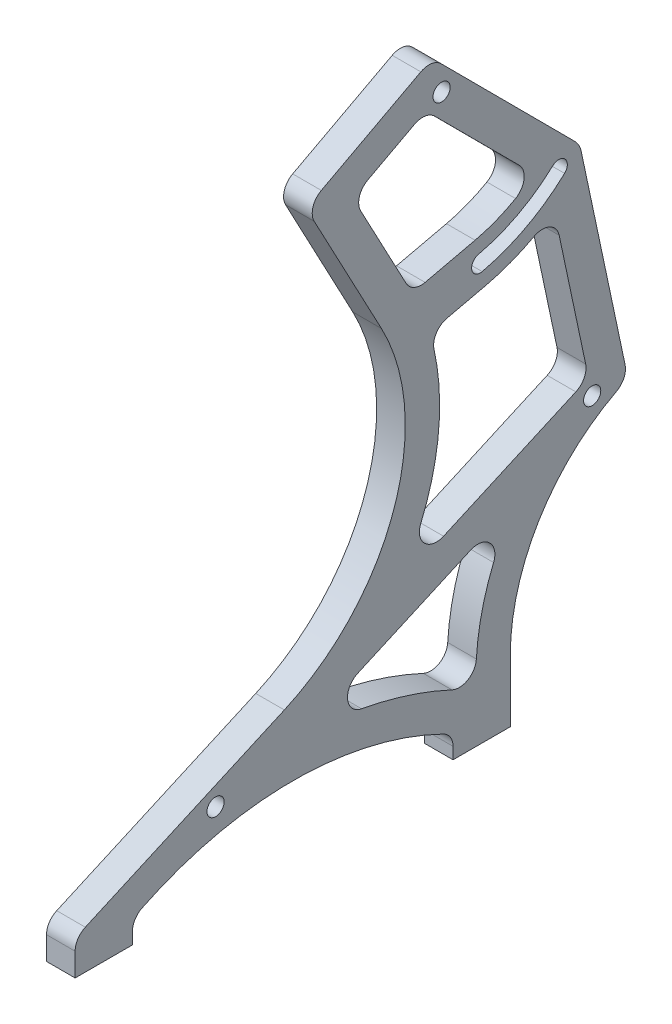
SolidWorks part; units mm, degrees
ref_plane "Front Plane" through (0, 0, 0) normal (0, 0, 1) x (1, 0, 0)
ref_plane "Top Plane" through (0, 0, 0) normal (0, 1, 0) x (1, 0, 0)
ref_plane "Right Plane" through (0, 0, 0) normal (1, 0, 0) x (0, 0, -1)
sketch "Sketch1" plane through (0, 0, 0) normal (1, 0, 0) x (0, 0, -1)
  line L0 (0, 0) -> (0, 6)
  line L1 (0, 6) -> (95.2678, 48.416) construction
  line L2 (95.2678, 48.416) -> (96.5419, 42.4154)
  line L3 (96.5419, 42.4154) -> (10, 3.8845) construction
  line L4 (66, 3.8845) -> (66, 0)
  line L5 (10, 3.8845) -> (10, 0)
  line L6 (10, 0) -> (0, 0)
  line L7 (66, 0) -> (76, 0)
  line L8 (76, 0) -> (76, 10.7836)
  line L9 (77.1303, 33.7728) -> (39.0321, 16.8104)
  line L10 (70, 8.542) -> (70, 10.7836)
  line L11 (70.7485, 72.7689) -> (64, 102) construction
  line L12 (64, 102) -> (84.46, 80.0594) construction
  line L13 (0, 6) -> (36.5418, 22.2695)
  line L14 (62.3411, 107.9134) -> (40.3467, 96.2188)
  line L15 (40.3467, 96.2188) -> (53.492, 71.4962)
  line L17 (62.3411, 107.9134) -> (87.2928, 82.8834)
  line L18 (64, 102) -> (78.0841, 75.5116) construction
  line L19 (46.9194, 83.8575) -> (78.3511, 100.5701) construction
  line L20 (88.3727, 80.8902) -> (95.2678, 48.416)
  line L21 (56.2016, 31.0226) -> (89.6638, 45.9209)
  line L22 (89.6638, 45.9209) -> (83.6484, 74.2522)
  line L23 (80.1087, 81.5914) -> (61.2314, 100.5279)
  line L24 (61.2314, 100.5279) -> (48.4613, 93.7379)
  line L25 (48.4613, 93.7379) -> (58.8843, 74.135)
  line L26 (58.8843, 74.135) -> (69.8487, 76.6664)
  line L27 (61.9365, 66.6293) -> (71.6483, 68.8714)
  arc A0 (10, 3.8845) -> (66, 3.8845) centre (38, -49.1815) cw
  arc A1 (96.5419, 42.4154) -> (76, 10.7836) centre (110.6253, 10.7836) ccw
  arc A2 (39.0321, 16.8104) -> (70, 8.542) centre (38, -49.1815) cw
  arc A3 (70, 10.7836) -> (77.1303, 33.7728) centre (110.6253, 10.7836) cw
  circle A4 centre (64, 102) radius 1.5
  arc A5 (84.46, 80.0594) -> (70.7485, 72.7689) centre (64, 102) cw construction
  arc A6 (71.086, 71.3073) -> (85.4829, 78.9624) centre (64, 102) ccw
  arc A7 (70.4111, 74.2305) -> (83.437, 81.1564) centre (64, 102) ccw
  arc A8 (70.4111, 74.2305) -> (71.086, 71.3073) centre (70.7485, 72.7689) ccw
  arc A9 (85.4829, 78.9624) -> (83.437, 81.1564) centre (84.46, 80.0594) ccw
  arc A10 (71.6483, 68.8714) -> (83.6484, 74.2522) centre (64, 102) ccw
  arc A11 (53.492, 71.4962) -> (36.5418, 22.2695) centre (22.0645, 54.786) cw
  arc A12 (56.2016, 31.0226) -> (61.9365, 66.6293) centre (22.0645, 54.786) ccw
  circle A13 centre (70.7485, 72.7689) radius 4 construction
  arc A15 (69.8487, 76.6664) -> (80.1087, 81.5914) centre (64, 102) ccw
  arc A17 (87.2928, 82.8834) -> (88.3727, 80.8902) centre (84.46, 80.0594) cw
  point P24 (78.0841, 75.5116)
  dimension "D8" = 60
  dimension "D9" = 6
  dimension "D10" = 6
  dimension "D11" = 3
  dimension "D12" = 30
  dimension "D14" = 64
  dimension "D21" = 6
  dimension "D24" = 6
  dimension "D25" = 1.5
  dimension "D32" = 4
  dimension "D33" = 8
  dimension "D18" = 4
  dimension "D1" = 6
  dimension "D2" = 24
  dimension "D3" = 102
  dimension "D4" = 10
  dimension "D5" = 10
  dimension "D6" = 6
  dimension "D7" = 56
  dimension "D13" = 102
  dimension "D15" = 62
  dimension "D16" = 30
  dimension "D17" = 6
  dimension "D19" = 28
  dimension "D20" = 3
  dimension "D22" = 40
  dimension "D27" = 12
  dimension "D28" = 6
  dimension "D29" = 6
  dimension "D31" = 6
extrude "Boss-Extrude1" add sketch "Sketch1" along normal blind 5
fillet "Fillet1" radius 3 17 edges at (2.5, 3.8845, -66) (2.5, 3.8845, -10) (2.5, 42.4154, -96.5419) (2.5, 16.8104, -39.0321) (2.5, 33.7728, -77.1303) (2.5, 8.542, -70) (2.5, 45.9209, -89.6638) (2.5, 31.0226, -56.2016) (2.5, 81.5914, -80.1087) (2.5, 107.9134, -62.3411) (2.5, 100.5279, -61.2314) (2.5, 93.7379, -48.4613) (2.5, 74.135, -58.8843) (2.5, 6, 0) (2.5, 66.6293, -61.9365) (2.5, 74.2522, -83.6484) (2.5, 96.2188, -40.3467)
hole_wizard "Tap Drill for M3 Tap1" positions "Sketch4" profile "Sketch3" hole size "M3" standard "ISO"
sketch "Sketch4" plane through (0, 0, 0) normal (0, -1, 0) x (-1, 0, 0)
  line L0 (0, 0) -> (0, 10) construction
  line L1 (-5, 0) -> (0, 0) construction
  point P0 (-2.5, 5.5)
  point P2 (-2.5, 70.5)
  dimension "D1" = 2.5
  dimension "D2" = 5.5
  dimension "D3" = 65
sketch "Sketch3" plane through (2.5, 0, -5.5) normal (1, 0, 0) x (0, 0, -1)
  line L0 (0, 0) -> (0, 7.7511)
  line L1 (0, 7.7511) -> (1.25, 7)
  line L2 (1.25, 7) -> (1.25, 0)
  line L5 (1.25, 0) -> (0, 0)
  line L10 (0, 7.7511) -> (-1.25, 7) construction
  line L11 (0, -6.35) -> (0, 107.95) construction
  dimension "Hole Dia." = 2.5
  dimension "Hole Depth" = 7
  dimension "Drill Angle" = 118
sketch "Sketch7" plane through (5, 0, 0) normal (1, 0, 0) x (0, 0, -1)
  line L0 (36.5418, 22.2695) -> (1.7798, 6.7924) construction
  line L3 (64.345, 34.6482) -> (87.445, 44.933) construction
  line L4 (96.0544, 44.7117) -> (88.3727, 80.8902) construction
  circle A0 centre (24.5256, 13.6356) radius 1.5
  circle A1 centre (90.3009, 42.9206) radius 1.5
  dimension "D1" = 3
  dimension "D4" = 72
  dimension "D2" = 3
  dimension "D3" = 3
  dimension "D5" = 6
extrude "Cut-Extrude2" cut sketch "Sketch7" against normal up to next
equation "\"ˇ3\"=3.9176"
